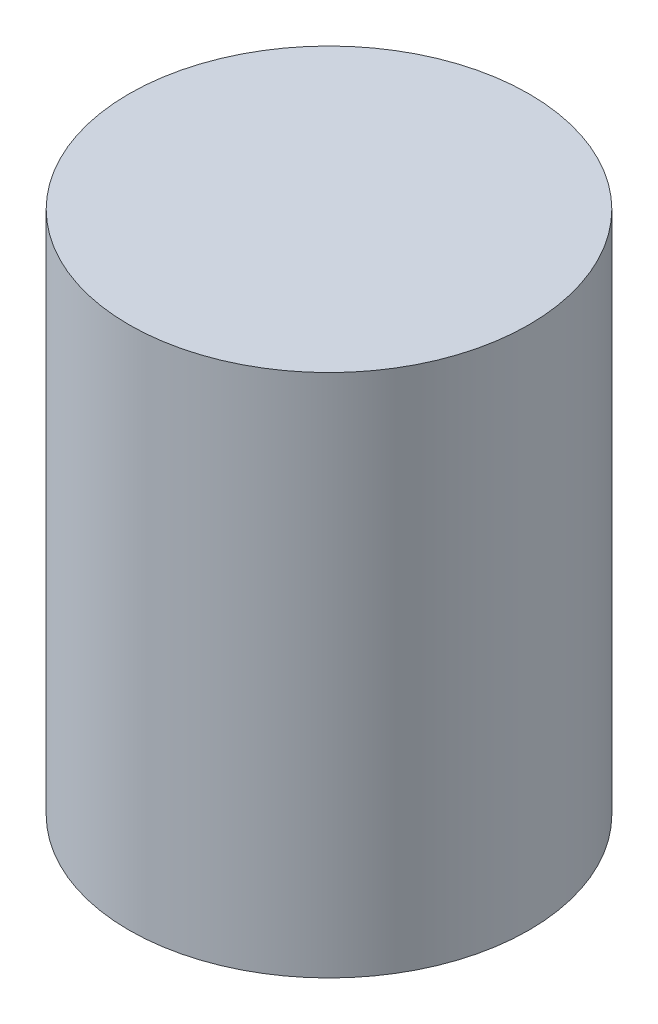
SolidWorks part; units mm, degrees
material "1060-O (SS)"
ref_plane "Front Plane" through (0, 0, 0) normal (0, 0, 1) x (1, 0, 0)
ref_plane "Top Plane" through (0, 0, 0) normal (0, 1, 0) x (1, 0, 0)
ref_plane "Right Plane" through (0, 0, 0) normal (1, 0, 0) x (0, 0, -1)
sketch "Sketch1" plane through (0, 0, 0) normal (0, 1, 0) x (1, 0, 0)
  circle A0 centre (0, 0) radius 24.9
  point P4 (0, 0)
  dimension "D1" = 49.8
extrude "Boss-Extrude1" add sketch "Sketch1" along normal blind 65.278 contours A0
